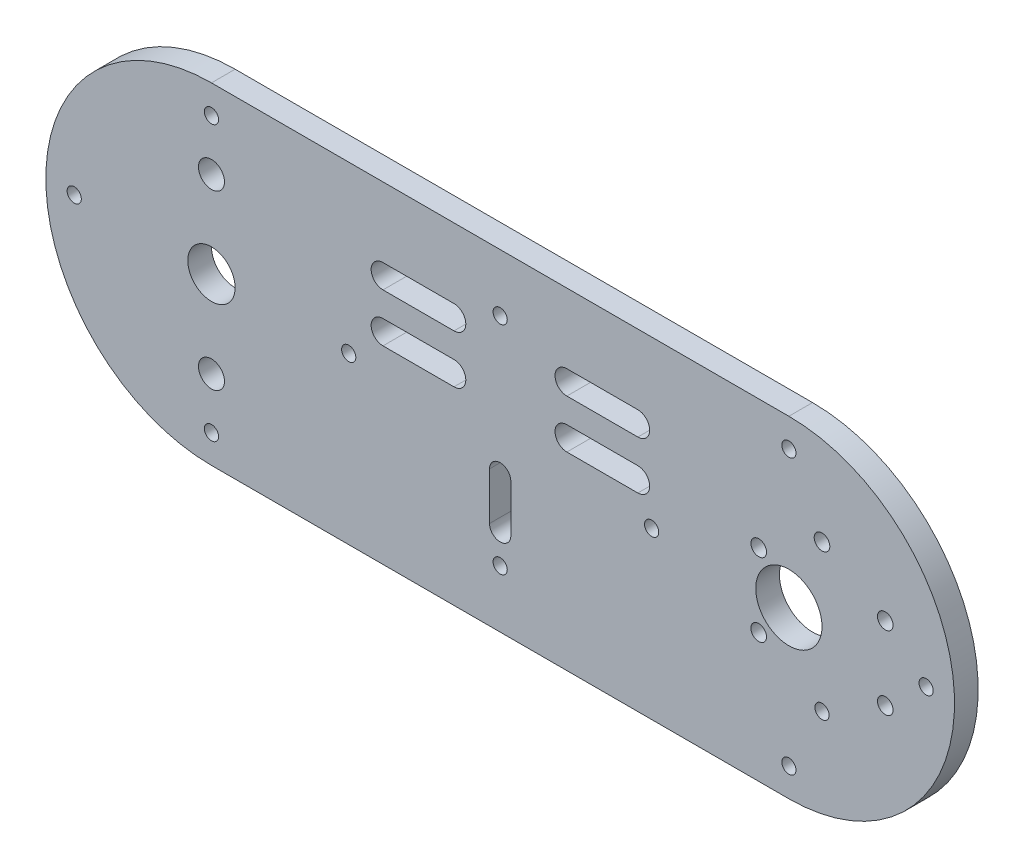
SolidWorks part; units mm, degrees
ref_plane "Front Plane" through (0, 0, 0) normal (0, 0, 1) x (1, 0, 0)
ref_plane "Top Plane" through (0, 0, 0) normal (0, 1, 0) x (1, 0, 0)
ref_plane "Right Plane" through (0, 0, 0) normal (1, 0, 0) x (0, 0, -1)
sketch "Sketch1" plane through (0, 0, 0) normal (0, 0, 1) x (1, 0, 0)
  line L0 (61, 0) -> (-61, 0) construction
  line L1 (-61, 5) -> (-24.76, 5) construction
  line L2 (61, -35) -> (-61, -35)
  line L3 (61, 35) -> (-61, 35)
  line L4 (0, -6.25) -> (0, -16.25) construction
  line L6 (2.25, -6.25) -> (2.25, -16.25)
  line L7 (-2.25, -6.25) -> (-2.25, -16.25)
  line L12 (-9.76, 7.5) -> (14.09, 7.5) construction
  line L13 (-24.76, 7.5) -> (-9.76, 7.5) construction
  line L14 (-24.76, 17.74) -> (-9.76, 17.74) construction
  line L15 (-24.76, 10) -> (-9.76, 10)
  line L16 (-24.76, 5) -> (-9.76, 5)
  line L17 (14.09, 7.5) -> (29.09, 7.5) construction
  line L18 (-24.76, 20.24) -> (-9.76, 20.24)
  line L19 (-24.76, 15.24) -> (-9.76, 15.24)
  line L21 (14.09, 10) -> (29.09, 10)
  line L22 (14.09, 5) -> (29.09, 5)
  line L23 (14.09, 17.74) -> (29.09, 17.74) construction
  line L25 (14.09, 20.24) -> (29.09, 20.24)
  line L26 (14.09, 15.24) -> (29.09, 15.24)
  arc A0 (61, -35) -> (61, 35) centre (61, 0) ccw
  arc A1 (-61, 35) -> (-61, -35) centre (-61, 0) ccw
  circle A2 centre (61, 0) radius 7
  circle A3 centre (-61, 0) radius 5
  circle A4 centre (-61, -29) radius 1.5
  circle A5 centre (-61, 29) radius 1.5
  circle A6 centre (61, 29) radius 1.5
  circle A7 centre (61, -29) radius 1.5
  circle A8 centre (0, -22.8728) radius 1.5
  circle A9 centre (0, 22.8728) radius 1.5
  circle A10 centre (-61, 18.25) radius 2.75
  circle A11 centre (-61, -18.25) radius 2.75
  circle A12 centre (-90, 0) radius 1.5
  circle A13 centre (-32, 0) radius 1.5
  arc A14 (2.25, -6.25) -> (-2.25, -6.25) centre (0, -6.25) ccw
  arc A15 (-2.25, -16.25) -> (2.25, -16.25) centre (0, -16.25) ccw
  circle A16 centre (90, 0) radius 1.5
  circle A17 centre (32, 0) radius 1.5
  circle A19 centre (68, -15.5) radius 1.5
  circle A20 centre (68, 15.5) radius 1.65
  circle A21 centre (54.6305, 7.7559) radius 1.65
  circle A22 centre (54.6305, -7.7559) radius 1.65
  circle A23 centre (81.3695, -7.7559) radius 1.65
  circle A24 centre (81.3695, 7.7559) radius 1.65
  arc A26 (-24.76, 10) -> (-24.76, 5) centre (-24.76, 7.5) ccw
  arc A27 (-9.76, 5) -> (-9.76, 10) centre (-9.76, 7.5) ccw
  arc A28 (-24.76, 20.24) -> (-24.76, 15.24) centre (-24.76, 17.74) ccw
  arc A29 (-9.76, 15.24) -> (-9.76, 20.24) centre (-9.76, 17.74) ccw
  arc A30 (14.09, 10) -> (14.09, 5) centre (14.09, 7.5) ccw
  arc A31 (29.09, 5) -> (29.09, 10) centre (29.09, 7.5) ccw
  arc A32 (14.09, 20.24) -> (14.09, 15.24) centre (14.09, 17.74) ccw
  arc A33 (29.09, 15.24) -> (29.09, 20.24) centre (29.09, 17.74) ccw
  point P5 (0, 0)
  point P27 (-61, 0)
  point P32 (-61, 0)
  point P39 (0, -11.25)
  point P63 (-17.26, 7.5)
  point P71 (-17.26, 17.74)
  point P78 (21.59, 7.5)
  point P86 (21.59, 17.74)
  dimension "D1" = 14
  dimension "D2" = 10
  dimension "D3" = 6
  dimension "D4" = 3
  dimension "D5" = 6
  dimension "D6" = 3
  dimension "D8" = 3
  dimension "D9" = 3
  dimension "D12" = 3
  dimension "D13" = 3
  dimension "D14" = 70
  dimension "D15" = 5.5
  dimension "D16" = 5.5
  dimension "D19" = 3
  dimension "D20" = 3
  dimension "D24" = 29
  dimension "D25" = 3
  dimension "D26" = 3
  dimension "D27" = 7
  dimension "D28" = 3.3
  dimension "D29" = 3
  dimension "D30" = 3.3
  dimension "D31" = 3.3
  dimension "D32" = 3.3
  dimension "D33" = 3.3
  dimension "D34" = 7
  dimension "D7" = 122
  dimension "D10" = 6
  dimension "D11" = 6
  dimension "D17" = 36.5
  dimension "D18" = 58
  dimension "D21" = 4.5
  dimension "D22" = 10
  dimension "D23" = 29
  dimension "D35" = 36.24
  dimension "D36" = 15
  dimension "D37" = 5
  dimension "D38" = 5.24
  dimension "D39" = 5.24
  dimension "D40" = 23.85
  dimension "D41" = 5
  dimension "D42" = 15
  dimension "D43" = 15
  dimension "D44" = 5
extrude "Boss-Extrude1" add sketch "Sketch1" along normal blind 5
